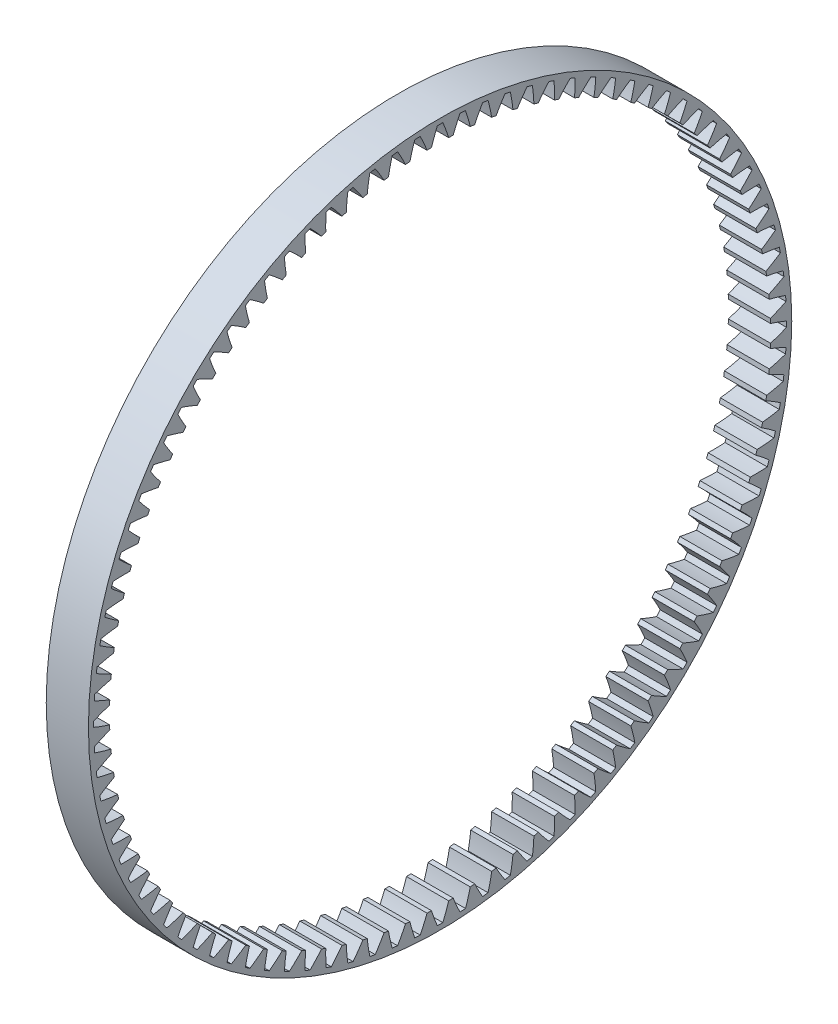
SolidWorks part; units mm, degrees
ref_plane "Plane1" through (0, 0, 0) normal (0, 0, 1) x (1, 0, 0)
ref_plane "Plane2" through (0, 0, 0) normal (0, 1, 0) x (1, 0, 0)
ref_plane "Plane3" through (0, 0, 0) normal (1, 0, 0) x (0, 0, -1)
sketch "HoldingSke" plane through (0, 0, 0) normal (0, 1, 0) x (1, 0, 0)
  line L0 (0, 0) -> (-0.2091, -1.989)
  line L1 (-15, 0) -> (100, 0) construction
  line L2 (0, 0) -> (-2.1039, 2.3779)
  line L3 (0, 0) -> (-11.863, 4.5341)
  line L4 (0, 0) -> (-0.9027, 8.5887)
  line L5 (0, 0) -> (-23.7986, -8.8762)
  line L6 (0, 0) -> (-10.5278, -7.1032)
  line L7 (-2.1039, 2.3779) -> (3.3635, 27.1825)
  line L8 (-76.2, 2.8779) -> (-54.61, 2.8779)
  line L9 (-71.009, 38.7566) -> (-53.1078, 45.2721)
  line L10 (-76.2, 71.12) -> (104.1128, 71.12)
  line L11 (0, 0) -> (-3, 0)
  line L12 (-76.2, 101.6) -> (-76.181, 101.6)
  line L13 (24.9733, 27.94) -> (52.9518, 28.4284)
  line L14 (24.9733, 27.94) -> (24.9743, 27.94)
  line L15 (24.9733, 27.94) -> (100.4006, 29.5858)
  circle A0 centre (0, 0) radius 25
  circle A1 centre (0, 0) radius 12.7
  circle A2 centre (0, 0) radius 12.7
  dimension "Num_teeth" = 96
  dimension "Pitch_radius" = 180.3128
  dimension "Width" = 3
  dimension "Diameter" = 50
sketch "BasProSke" plane through (0, 0, 0) normal (0, 1, 0) x (1, 0, 0)
  line L0 (-10, 0) -> (60, 0) construction
  line L1 (0, 23.5) -> (0, 25)
  line L2 (0, 23.5) -> (3, 23.5)
  line L3 (3, 23.5) -> (3, 25)
  line L4 (3, 25) -> (0, 25)
  dimension "Thickness" = 3
  dimension "Diameter" = 50
revolve "Base-Revolve" add sketch "BasProSke" angle 360 about L0
sketch "TooCutSke" plane through (0, 0, 0) normal (1, 0, 0) x (0, 0, -1)
  line L3 (0.4402, 23.996) -> (0.4402, 53.6633) construction
  line L4 (0, 0) -> (0, 59.563) construction
  line L5 (0, 0) -> (-2.2356, 68.2909) construction
  line L6 (-10.8582, 19.9528) -> (37.1584, 21.5247) construction
  circle A0 centre (0, 0) radius 24 construction
  circle A1 centre (0, 0) radius 24.626 construction
  circle A2 centre (0, 0) radius 20.2974 construction
  circle A3 centre (0, 0) radius 23.4746 construction
  arc A4 (0.6159, 23.4665) -> (0.1948, 24.6252) centre (-10.8582, 19.9528) ccw
  arc A5 (0.6159, 23.4665) -> (-0.6159, 23.4665) centre (0, 0) ccw
  arc A6 (0.1948, 24.6252) -> (-0.1948, 24.6252) centre (0, 0) ccw
  arc A7 (-0.1948, 24.6252) -> (-0.6159, 23.4665) centre (10.8582, 19.9528) ccw
extrude "ToothCut" cut sketch "TooCutSke" along normal through all
fillet "Breaks" [suppressed] radius 0.05
fillet "RootFillets" [suppressed] radius 0.126
pattern_circular "TeethCuts" count 96 every 3.75 about axis through (-10, 0, 0) along (1, 0, 0) of "RootFillets", "Breaks", "ToothCut"
equation "' \"Module@HoldingSke\" = 6.35"
equation "' \"Num_teeth@HoldingSke\" = 24"
equation "' \"Ap@HoldingSke\" =  14.5"
equation "' \"Ap@HoldingSke\" = 14.5"
equation "' \"Width@HoldingSke\" = 12"
equation "' \"Diameter@HoldingSke\" = 8 * 25.4"
equation "' \"Show_teeth@HoldingSke\" = 100"
equation "' \"Backlash@HoldingSke\" = 0.009 * 25.4"
equation "' \"Addendum_fac@HoldingSke\" = 1.0"
equation "' \"Dedendum_fac@HoldingSke\" = 1.25"
equation "' \"Dedendum_add@HoldingSke\" = 0.00005 * 25.4"
equation "' \"Clearance_fac@HoldingSke\" = 0.25"
equation "\"Pitch@HoldingSke\" = 1 / \"Module@HoldingSke\" "
equation "\"Overcut_dia@TooCutSke\" = (\"Num_teeth@HoldingSke\" - 2 * \"Addendum_fac@HoldingSke\") / \"Pitch@HoldingSke\" - 0.002 * 25.4"
equation "\"Pitch_dia@TooCutSke\" = \"Num_teeth@HoldingSke\" / \"Pitch@HoldingSke\""
equation "\"Base_dia@TooCutSke\" = \"Num_teeth@HoldingSke\" / \"Pitch@HoldingSke\" * cos((\"Ap@HoldingSke\"  * 3.14159265 / 180)) * 0.90"
equation "\"Root_dia@TooCutSke\" = \"Num_teeth@HoldingSke\"  / \"Pitch@HoldingSke\" + 2 *  \"Dedendum_fac@HoldingSke\"/ \"Pitch@HoldingSke\" + \"Dedendum_add@HoldingSke\" * 2"
equation "\"Half_ang@TooCutSke\" = 180 / \"Num_teeth@HoldingSke\""
equation "\"Half_CT@TooCutSke\" = \"Num_teeth@HoldingSke\" / \"Pitch@HoldingSke\" * sin((3.14159265 / 2 / \"Num_teeth@HoldingSke\")) / 2 + 10 * \"Backlash@HoldingSke\" / 4"
equation "\"Flank_rad@TooCutSke\" = \"Num_teeth@HoldingSke\" / \"Pitch@HoldingSke\" / 4"
equation "\"Radius@RootFillets\"= \"Clearance_fac@HoldingSke\" / \"Pitch@HoldingSke\" + \"Dedendum_add@HoldingSke\""
equation "\"Break_rad@Breaks\" = 0.02 / \"Pitch@HoldingSke\" * 5"
equation "\"Num_teeth@TeethCuts\" = int( \"Show_teeth@HoldingSke\" ) + 1"
equation "\"Num_teeth@TeethCuts\" = ((sgn( \"Num_teeth@TeethCuts\" - \"Num_teeth@HoldingSke\" )-1)*( \"Num_teeth@TeethCuts\" - \"Num_teeth@HoldingSke\" ))/-2+ \"Num_teeth@HoldingSke\""
equation "\"Num_teeth@TeethCuts\" = ((sgn( \"Num_teeth@TeethCuts\" - 2.0)+1)*( \"Num_teeth@TeethCuts\" - 2.0))/2 +2.0"
equation "\"Angle@TeethCuts\" = 360.0 / \"Num_teeth@HoldingSke\""
equation "\"Diameter@BasProSke\" = \"Num_teeth@HoldingSke\"  / \"Pitch@HoldingSke\" + 2 *  \"Dedendum_fac@HoldingSke\"/ \"Pitch@HoldingSke\" + \"Dedendum_add@HoldingSke\" * 2 + 0.002 * 25.4"
equation "\"Diameter@BasProSke\" = ((sgn( \"Diameter@BasProSke\"  - \"Diameter@HoldingSke\" )+1)*( \"Diameter@BasProSke\"  - \"Diameter@HoldingSke\" ))/2 + \"Diameter@HoldingSke\""
equation "\"Inside_diameter@BasProSke\" =  (\"Num_teeth@HoldingSke\" - 2 * \"Addendum_fac@HoldingSke\") / \"Pitch@HoldingSke\" "
equation "\"Thickness@BasProSke\"  = \"Width@HoldingSke\""
